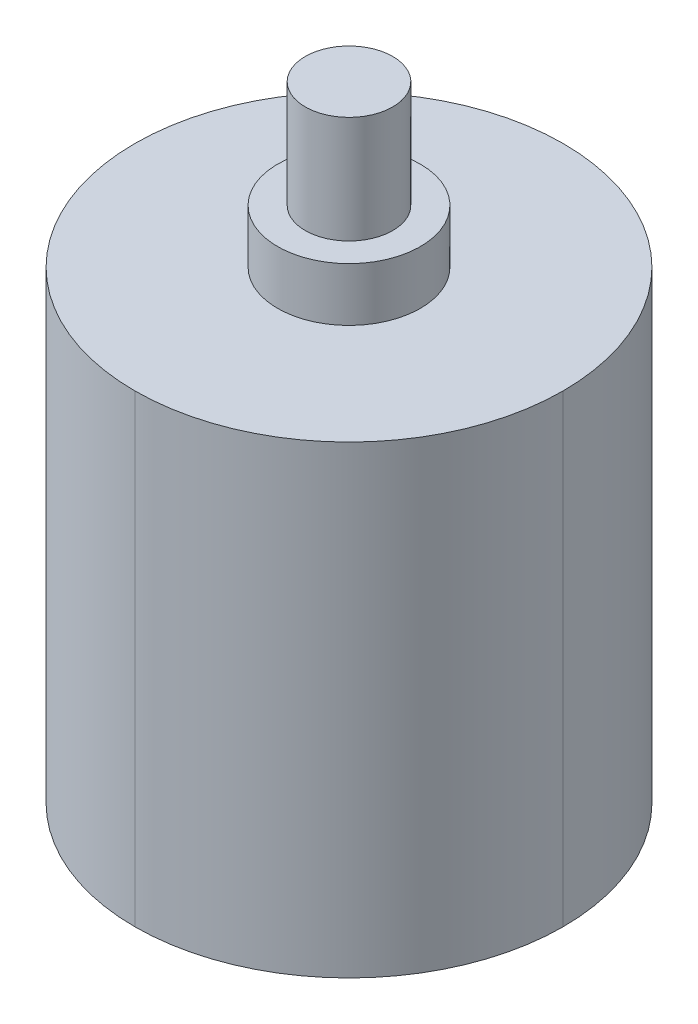
SolidWorks part; units mm, degrees
ref_plane "Front Plane" through (0, 0, 0) normal (0, 0, 1) x (1, 0, 0)
ref_plane "Top Plane" through (0, 0, 0) normal (0, 1, 0) x (1, 0, 0)
ref_plane "Right Plane" through (0, 0, 0) normal (1, 0, 0) x (0, 0, -1)
sketch "Sketch3" plane through (0, 0, 0) normal (0, 1, 0) x (1, 0, 0)
  line L1 (0, 0) -> (-30.48, 0)
  line L2 (0, 0) -> (0, 30.48)
  line L3 (0, 30.48) -> (-30.48, 30.48)
  line L4 (-30.48, 0) -> (-30.48, 30.48)
  dimension "D1" = 30.48
  dimension "D2" = 30.48
extrude "Boss-Extrude1" add sketch "Sketch3" along normal blind 33.02
sketch "Sketch4" plane through (0, 33.02, 0) normal (0, 1, 0) x (1, 0, 0)
  line L0 (-30.48, 30.48) -> (-30.48, 0) construction
  line L1 (0, 30.48) -> (-30.48, 30.48) construction
  circle A0 centre (-15.24, 15.24) radius 5.08
  point P4 (-30.48, 15.24)
  point P7 (-15.24, 30.48)
  dimension "D1" = 10.16
extrude "Boss-Extrude2" add sketch "Sketch4" along normal blind 3.81
sketch "Sketch5" plane through (0, 36.83, 0) normal (0, 1, 0) x (1, 0, 0)
  circle A0 centre (-15.24, 15.24) radius 3.1115
  circle A1 centre (-15.24, 15.24) radius 5.08 construction
  circle A2 centre (-15.24, 15.24) radius 5.08 construction
  dimension "D1" = 6.223
extrude "Boss-Extrude3" add sketch "Sketch5" along normal blind 7.62
sketch "Sketch6" plane through (0, 0, 0) normal (0, -1, 0) x (1, 0, 0)
  line L0 (-30.48, -30.48) -> (-30.48, 0) construction
  line L1 (-30.48, 0) -> (0, 0) construction
  circle A0 centre (-15.24, -15.24) radius 10.8585
  point P4 (-30.48, -15.24)
  point P7 (-15.24, 0)
  dimension "D1" = 21.717
extrude "Cut-Extrude1" cut sketch "Sketch6" against normal blind 25.4
fillet "Fillet1" radius 15.24 4 edges at (-30.48, 16.51, -30.48) (0, 16.51, -30.48) (-30.48, 16.51, 0) (0, 16.51, 0)
